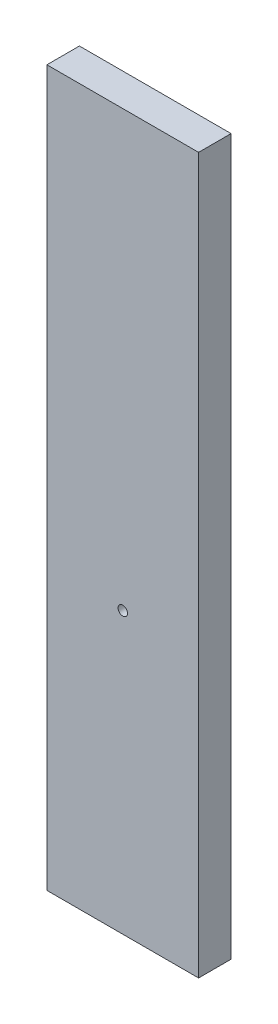
SolidWorks part; units mm, degrees
ref_plane "Front Plane" through (0, 0, 0) normal (0, 0, 1) x (1, 0, 0)
ref_plane "Top Plane" through (0, 0, 0) normal (0, 1, 0) x (1, 0, 0)
ref_plane "Right Plane" through (0, 0, 0) normal (1, 0, 0) x (0, 0, -1)
sketch "Sketch1" plane through (0, 0, 0) normal (0, 1, 0) x (1, 0, 0)
  line L1 (0, 0) -> (88.9, 0)
  line L2 (0, 0) -> (0, 19.05)
  line L3 (0, 19.05) -> (88.9, 19.05)
  line L4 (88.9, 0) -> (88.9, 19.05)
  dimension "D1" = 19.05
  dimension "D2" = 88.9
extrude "Boss-Extrude1" add sketch "Sketch1" along normal blind 419.1
sketch "Sketch2" plane through (0, 0, 0) normal (0, 0, 1) x (1, 0, 0)
  line L0 (44.45, 419.1) -> (44.45, 164.2776) construction
  line L1 (0, 419.1) -> (88.9, 419.1) construction
  line L2 (-349.25, 253.6518) -> (44.45, 164.2776) construction
  line L3 (-349.25, 253.6518) -> (-39.4224, 253.6518) construction
  circle A0 centre (44.45, 164.2776) radius 2.7781
  circle A1 centre (-349.25, 253.6518) radius 2.7781 construction
  circle A2 centre (-349.25, 253.6518) radius 2.7781 construction
  dimension "D1" = 5.5562
  dimension "D2" = 12.79
extrude "Cut-Extrude1" cut sketch "Sketch2" against normal through all
